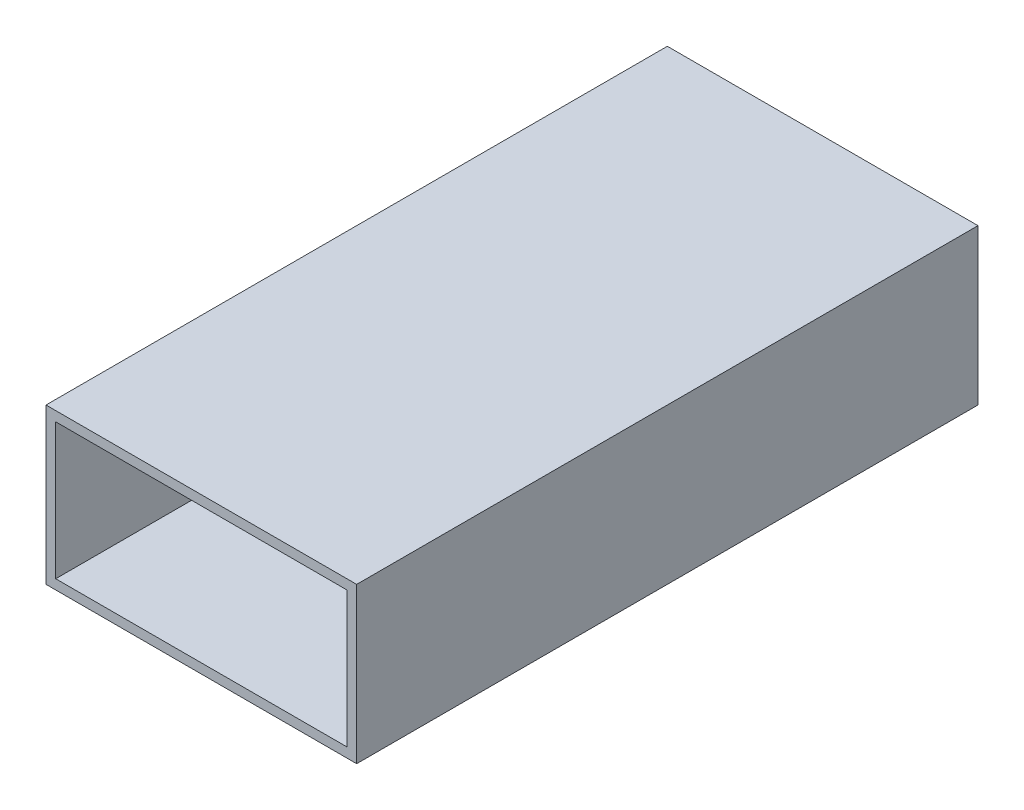
SolidWorks part; units mm, degrees
material "6061-T6 (SS)"
ref_plane "Front Plane" through (0, 0, 0) normal (0, 0, 1) x (1, 0, 0)
ref_plane "Top Plane" through (0, 0, 0) normal (0, 1, 0) x (1, 0, 0)
ref_plane "Right Plane" through (0, 0, 0) normal (1, 0, 0) x (0, 0, -1)
sketch "Sketch1" plane through (0, 0, 0) normal (0, 0, 1) x (1, 0, 0)
  line L1 (-25.4, -12.7) -> (25.4, -12.7)
  line L2 (-25.4, -12.7) -> (-25.4, 12.7)
  line L3 (-25.4, 12.7) -> (25.4, 12.7)
  line L4 (25.4, -12.7) -> (25.4, 12.7)
  line L5 (-25.4, -12.7) -> (25.4, 12.7) construction
  line L6 (-25.4, 12.7) -> (25.4, -12.7) construction
  line L7 (-23.8125, -11.1125) -> (23.8125, -11.1125)
  line L8 (-23.8125, -11.1125) -> (-23.8125, 11.1125)
  line L9 (-23.8125, 11.1125) -> (23.8125, 11.1125)
  line L10 (23.8125, -11.1125) -> (23.8125, 11.1125)
  line L11 (-23.8125, -11.1125) -> (23.8125, 11.1125) construction
  line L12 (-23.8125, 11.1125) -> (23.8125, -11.1125) construction
  point P0 (0, 0)
  point P6 (0, 0)
  dimension "D1" = 50.8
  dimension "D2" = 25.4
  dimension "D3" = 1.5875
  dimension "D4" = 1.5875
extrude "Boss-Extrude1" add sketch "Sketch1" along normal mid plane 101.6
